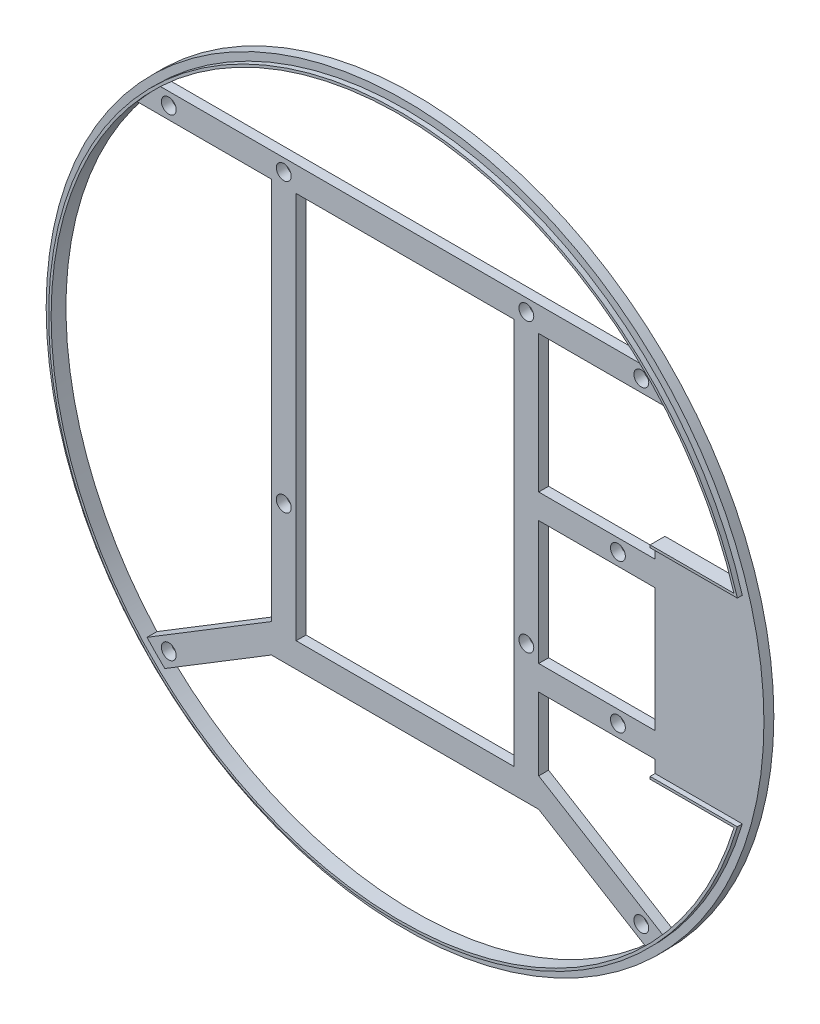
SolidWorks part; units mm, degrees
material "ABS"
ref_plane "Ebene vorne" through (0, 0, 0) normal (0, 0, 1) x (1, 0, 0)
ref_plane "Ebene oben" through (0, 0, 0) normal (0, 1, 0) x (1, 0, 0)
ref_plane "Ebene rechts" through (0, 0, 0) normal (1, 0, 0) x (0, 0, -1)
sketch "Skizze1" plane through (0, 0, 0) normal (0, 0, 1) x (1, 0, 0)
  circle A0 centre (0, 0) radius 72.5
  circle A1 centre (0, 0) radius 70.5
  dimension "D1" = 145
  dimension "D2" = 2
extrude "Base Ring" add sketch "Skizze1" along normal blind 2
sketch "Placement Sketch" plane through (0, 0, 0) normal (0, 0, 1) x (1, 0, 0)
  line L0 (0, 143.896) -> (0, -183.6418) construction
  line L9 (-28, 49.4797) -> (28, 49.4797) construction
  line L10 (-28, 49.4797) -> (-28, -35.5203) construction
  line L11 (-28, -35.5203) -> (28, -35.5203) construction
  line L12 (28, 49.4797) -> (28, -35.5203) construction
  line L13 (-28, 49.4797) -> (28, -35.5203) construction
  line L14 (-28, -35.5203) -> (28, 49.4797) construction
  line L15 (47.7297, 47.7297) -> (-47.7297, 47.7297) construction
  line L16 (-47.7297, 47.7297) -> (-47.7297, -47.7297) construction
  line L17 (-47.7297, -47.7297) -> (47.7297, -47.7297) construction
  line L18 (47.7297, -47.7297) -> (47.7297, 47.7297) construction
  line L19 (-24.5, 47.7297) -> (24.5, 47.7297) construction
  line L20 (-24.5, 47.7297) -> (-24.5, -10.2703) construction
  line L21 (-24.5, -10.2703) -> (24.5, -10.2703) construction
  line L22 (24.5, 47.7297) -> (24.5, -10.2703) construction
  line L23 (-24.5, 47.7297) -> (24.5, -10.2703) construction
  line L24 (-24.5, -10.2703) -> (24.5, 47.7297) construction
  circle A0 centre (0, 0) radius 67.5 construction
  circle A1 centre (0, 0) radius 47.7297 construction
  point P2 (0, 6.9797)
  point P8 (0, 18.7297)
  dimension "D1" = 135
  dimension "D2" = 56
  dimension "D3" = 85
  dimension "D5" = 49
  dimension "D6" = 58
  dimension "D7" = 1.75
sketch "Skizze2" plane through (0, 0, 0) normal (0, 0, 1) x (1, 0, 0)
  line L1 (-54.0789, 50.2297) -> (0, 50.2297)
  line L2 (-54.0789, 50.2297) -> (-54.0789, 45.2297)
  line L3 (-54.0789, 45.2297) -> (0, 45.2297)
  line L4 (0, 50.2297) -> (0, 45.2297)
  line L5 (-54.0789, 50.2297) -> (0, 45.2297) construction
  line L6 (-54.0789, 45.2297) -> (0, 50.2297) construction
  line L7 (-47.7297, -47.7297) -> (-28, -35.5203) construction
  line L8 (0, 143.896) -> (0, -183.6418) construction
  line L9 (47.7297, 47.7297) -> (-47.7297, 47.7297) construction
  line L10 (-24.5, 47.7297) -> (-24.5, -10.2703) construction
  line L11 (-27, -33.0203) -> (-22, -33.0203)
  line L12 (-27, -33.0203) -> (-27, 45.2297)
  line L13 (-27, 45.2297) -> (-22, 45.2297)
  line L14 (-22, -33.0203) -> (-22, 45.2297)
  line L15 (-27, -33.0203) -> (-22, 45.2297) construction
  line L16 (-27, 45.2297) -> (-22, -33.0203) construction
  line L17 (-28, -35.5203) -> (28, -35.5203) construction
  line L18 (-27, -38.0203) -> (0, -38.0203)
  line L19 (-27, -38.0203) -> (-27, -33.0203)
  line L20 (-27, -33.0203) -> (0, -33.0203)
  line L21 (0, -38.0203) -> (0, -33.0203)
  line L22 (-27, -38.0203) -> (0, -33.0203) construction
  line L23 (-27, -33.0203) -> (0, -38.0203) construction
  line L24 (-52.1174, -47.4766) -> (-27, -32.1644)
  line L25 (-48.5251, -51.1426) -> (-27, -38.0203)
  circle A0 centre (0, 0) radius 70.5
  circle A1 centre (0, 0) radius 70.5 construction
  point P5 (-27.0394, 47.7297)
  point P19 (-24.5, 6.1047)
  point P25 (-13.5, -35.5203)
  dimension "D1" = 5
  dimension "D2" = 5
  dimension "D3" = 5
  dimension "D4" = 5
  dimension "D5" = 2.5
extrude "Raspberry Frame" add sketch "Skizze2" along normal up to surface (2 mm away) contours L1 A0 L3 L4 | L11 L14 L3 L12 | L24 A0 L25 L19 L12 | L18 L21 L20 L11 L19 region at (-25.9413, 47.6927, 0) region at (-24.5, 6.1047, 0) region at (-38.6973, -42.1483, 0) region at (-13.5, -35.5203, 0) up to face at (72.5, 0, 2)
hole_wizard "Screws I" positions "Skizze3" profile "Skizze4" hole size "Ø3.5" standard "ISO" end condition through all
sketch "Skizze3" plane through (0, 0, 2) normal (0, 0, 1) x (1, 0, 0)
  point P0 (-47.7297, -47.7297)
  point P2 (-24.5, -10.2703)
  point P4 (-47.7297, 47.7297)
  point P6 (-24.5, 47.7297)
sketch "Skizze4" plane through (-47.7297, -47.7297, 2) normal (1, 0, 0) x (0, -1, 0)
  line L0 (0, 0) -> (0, 2)
  line L1 (0, 2) -> (1.5, 2)
  line L2 (1.5, 2) -> (1.5, 0)
  line L5 (1.5, 0) -> (0, 0)
  line L11 (0, -6.35) -> (0, 107.95) construction
  dimension "Bohrerdurchmesser" = 3
  dimension "Bohrungstiefe" = 2
mirror "Mirror I" about plane through (0, 0, 0) normal (1, 0, 0) of "Raspberry Frame", "Screws I"
sketch "Skizze6" plane through (0, 0, 0) normal (0, 0, 1) x (1, 0, 0)
  line L0 (54.0789, 45.2297) -> (27, 45.2297) construction
  line L1 (27, -32.1644) -> (27, 45.2297) construction
  line L2 (27, 17.5) -> (69.383, 17.5)
  line L3 (27, 17.5) -> (27, 12.5)
  line L4 (27, 12.5) -> (69.383, 12.5)
  line L5 (69.383, 17.5) -> (69.383, 12.5)
  line L6 (0, 0) -> (92.3585, 0) construction
  line L7 (27, -17.5) -> (69.383, -17.5)
  line L8 (27, -17.5) -> (27, -12.5)
  line L9 (27, -12.5) -> (69.383, -12.5)
  line L10 (69.383, -17.5) -> (69.383, -12.5)
  line L11 (27, 15) -> (69.383, 15) construction
  line L12 (27, -15) -> (69.383, -15) construction
  line L13 (43, 15) -> (43, -15) construction
  arc A0 (52.1174, -47.4766) -> (54.0789, 45.2297) centre (0, 0) ccw
  circle A1 centre (43, 15) radius 1.5
  circle A2 centre (43, -15) radius 1.5
  dimension "D1" = 5
  dimension "D3" = 3
  dimension "D2" = 30
  dimension "D4" = 43
extrude "Camera Beam" add sketch "Skizze6" along normal up to surface (2 mm away) contours L4 A0 L2 L3 A1 | L7 A0 L9 L8 A2 region at (48.1086, -14.9888, 0) region at (48.1086, 14.9888, 0) up to face at (49.2297, -47.7297, 2)
sketch "Skizze7" plane through (0, 0, 2) normal (0, 0, 1) x (1, 0, 0)
  line L0 (52.1174, -47.4766) -> (27, -32.1644) construction
  line L1 (0, 0) -> (84.5286, 0) construction
  line L3 (50.5, -20.5) -> (70.5, -20.5)
  line L4 (50.5, -20.5) -> (50.5, 20.5)
  line L5 (50.5, 20.5) -> (70.5, 20.5)
  line L6 (70.5, -20.5) -> (70.5, 20.5)
  line L7 (50.5, -20.5) -> (70.5, 20.5) construction
  line L8 (50.5, 20.5) -> (70.5, -20.5) construction
  arc A0 (54.0789, 45.2297) -> (52.1174, -47.4766) centre (0, 0) cw
  point P5 (60.5, 0)
  line M4 (69.383, -12.5) -> (27, -12.5)
  line M6 (27, 12.5) -> (69.383, 12.5)
  arc M7 (69.383, 12.5) -> (69.383, -12.5) centre (0, 0) cw
  arc M8 (54.0789, 45.2297) -> (68.2935, 17.5) centre (0, 0) cw
  line M9 (68.2935, 17.5) -> (27, 17.5)
  line M17 (27, -17.5) -> (68.2935, -17.5)
  arc M18 (68.2935, -17.5) -> (52.1174, -47.4766) centre (0, 0) cw
  dimension "D1" = 20
  dimension "D2" = 41
extrude "Bottom Cover" add sketch "Skizze7" against normal up to surface (2 mm away) contours L4 M4 M7 M6 | L5 L4 M9 M8 | L4 L3 M18 M17 region at (59.1944, -18.9879, 2) region at (60.3172, 0, 2) region at (59.1944, 18.9879, 2) up to face at (48.4707, 0, 0)
sketch "Skizze8" plane through (0, 0, 2) normal (0, 0, 1) x (1, 0, 0)
  line L0 (0, 0) -> (72.5, 0) construction
  line L4 (50.5, -20.5) -> (68.1249, -20.5)
  line L5 (50.5, -20.5) -> (50.5, -20)
  line L6 (50.5, -20) -> (68.1249, -20)
  line L7 (68.1249, -20.5) -> (68.1249, -20)
  line L8 (50.5, 20.5) -> (68.1249, 20.5)
  line L9 (50.5, 20.5) -> (50.5, 20)
  line L10 (50.5, 20) -> (68.1249, 20)
  line L11 (68.1249, 20.5) -> (68.1249, 20)
  arc A0 (67.4537, 20.5) -> (67.4537, -20.5) centre (0, 0) ccw
  arc A1 (67.4537, 20.5) -> (54.0789, 45.2297) centre (0, 0) ccw construction
  arc A2 (68.1249, 20) -> (68.1249, -20) centre (0, 0) ccw
  circle A3 centre (0, 0) radius 72.5 construction
  arc A4 (52.1174, -47.4766) -> (67.4537, -20.5) centre (0, 0) ccw construction
  point P8 (0, 0)
  point P9 (67.4537, -20.5)
  point P22 (68.0856, -20)
  point P23 (0, 0)
  point P25 (67.5331, -20)
  point P26 (0, 0)
  point P30 (0, 0)
  line M4 (50.5, -20.5) -> (67.4537, -20.5)
  arc M5 (67.4537, -20.5) -> (52.1174, -47.4766) centre (0, 0) cw
  line M9 (50.5, -17.5) -> (50.5, -20.5)
  arc M10 (54.0789, 45.2297) -> (67.4537, 20.5) centre (0, 0) cw
  line M11 (67.4537, 20.5) -> (50.5, 20.5)
  line M12 (50.5, 20.5) -> (50.5, 17.5)
  arc M25 (48.5251, -51.1426) -> (-48.5251, -51.1426) centre (0, 0) cw
  arc M36 (-52.1174, -47.4766) -> (-54.0789, 45.2297) centre (0, 0) cw
  arc M42 (-49.4694, 50.2297) -> (49.4694, 50.2297) centre (0, 0) cw
  dimension "D2" = 0.5
  dimension "D4" = 0.5
extrude "Inner Ring" add sketch "Skizze8" along normal blind 1 contours A2 A0 M5 M25 M36 M42 M10 | L10 A2 L8 M11 M12 | L4 A2 L6 M9 M4 region at (59.2755, -20.2496, 2) region at (67.7149, -20.6987, 2) region at (59.2755, 20.2496, 2)
equation "\"D_outer\"=145"
equation "\"D1@Skizze1\"=\"D_outer\""
